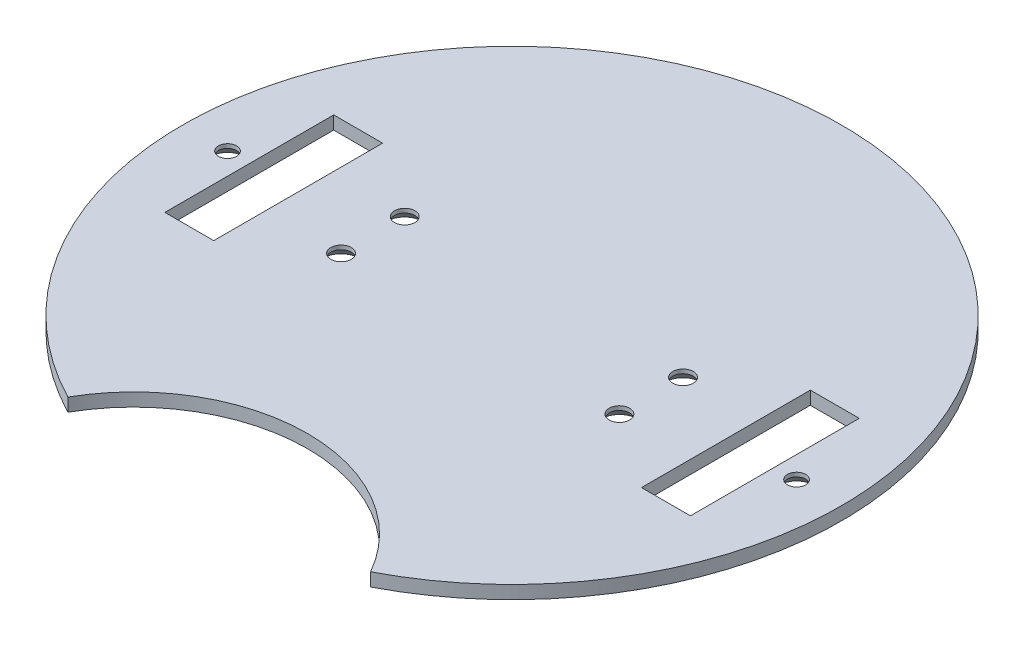
SolidWorks part; units mm, degrees
ref_plane "Front Plane" through (0, 0, 0) normal (0, 0, 1) x (1, 0, 0)
ref_plane "Top Plane" through (0, 0, 0) normal (0, 1, 0) x (1, 0, 0)
ref_plane "Right Plane" through (0, 0, 0) normal (1, 0, 0) x (0, 0, -1)
sketch "Sketch1" plane through (0, 0, 0) normal (0, 1, 0) x (1, 0, 0)
  line L0 (0, -83.2398) -> (-33.2911, -64.4046) construction
  line L1 (0, -83.2398) -> (0, 0) construction
  arc A0 (33.2911, -64.4046) -> (-33.2911, -64.4046) centre (0, 0) ccw
  arc A1 (33.2911, -64.4046) -> (-33.2911, -64.4046) centre (0, -83.2398) ccw
  dimension "D1" = 145
  dimension "D2" = 76.5
  dimension "D3" = 60.5
extrude "Boss-Extrude1" add sketch "Sketch1" along normal blind 2.9
sketch "solenoid placement" plane through (0, 2.9, 0) normal (0, 1, 0) x (1, 0, 0)
  line L0 (0, 0) -> (0, -36) construction
  line L1 (0, -36) -> (0, -44.9898) construction
  line L2 (-19, -36) -> (19, -36)
  line L3 (-19, -36) -> (-19, 28.4)
  line L4 (-19, 28.4) -> (19, 28.4)
  line L5 (19, -36) -> (19, 28.4)
  circle A1 centre (0, 0) radius 72.5 construction
  arc A2 (33.2911, -64.4046) -> (-33.2911, -64.4046) centre (0, 0) ccw construction
  arc A3 (33.2911, -64.4046) -> (-33.2911, -64.4046) centre (0, -83.2398) ccw construction
  dimension "D1" = 64.4
  dimension "D2" = 36
  dimension "D4" = 38
sketch "Sketch2" plane through (0, 2.9, 0) normal (0, 1, 0) x (1, 0, 0)
  line L1 (-57.5, 18.2695) -> (-47.34, 18.2695) construction
  line L2 (-57.5, 18.2695) -> (-57.5, -18.2695) construction
  line L3 (-57.5, -18.2695) -> (-47.34, -18.2695) construction
  line L4 (-47.34, 18.2695) -> (-47.34, -18.2695) construction
  line L8 (-57.8, -18.5695) -> (-47.04, -18.5695)
  line L9 (-47.04, 18.5695) -> (-47.04, -18.5695)
  line L10 (-57.8, 18.5695) -> (-47.04, 18.5695)
  line L11 (-57.8, 18.5695) -> (-57.8, -18.5695)
  line L12 (0, 0) -> (0, 72.5) construction
  line L13 (47.34, 18.2695) -> (47.34, -18.2695) construction
  line L14 (57.5, -18.2695) -> (47.34, -18.2695) construction
  line L15 (57.5, 18.2695) -> (57.5, -18.2695) construction
  line L16 (57.5, 18.2695) -> (47.34, 18.2695) construction
  line L17 (57.8, 18.5695) -> (57.8, -18.5695)
  line L18 (57.8, 18.5695) -> (47.04, 18.5695)
  line L19 (47.04, 18.5695) -> (47.04, -18.5695)
  line L20 (57.8, -18.5695) -> (47.04, -18.5695)
  arc A0 (33.2911, -64.4046) -> (-33.2911, -64.4046) centre (0, 0) ccw construction
extrude "Cut-Extrude1" cut sketch "Sketch2" against normal through all
sketch "Sketch3" plane through (0, 0, 0) normal (0, -1, 0) x (1, 0, 0)
  line L0 (0, 0) -> (0, -72.5) construction
  circle A0 centre (-62.58, 0) radius 2
  circle A1 centre (-30.61, 7) radius 2.25
  circle A2 centre (-30.61, -7) radius 2.25
  arc A3 (-33.2911, 64.4046) -> (33.2911, 64.4046) centre (0, 0) ccw construction
  circle A4 centre (30.61, -7) radius 2.25
  circle A5 centre (30.61, 7) radius 2.25
  circle A6 centre (62.58, 0) radius 2
  dimension "D1" = 4
  dimension "D2" = 4.5
extrude "Cut-Extrude2" cut sketch "Sketch3" against normal through all
chamfer "Chamfer1" distance 2 angle 41 6 edges at (-30.61, 0, -9.25) (-30.61, 0, 4.75) (-62.58, 0, -2) (62.58, 0, 2) (30.61, 0, 9.25) (30.61, 0, -4.75) first distance on face at (-30.61, 2.9, -9.25) first distance on face at (-30.61, 2.9, 4.75) first distance on face at (-62.58, 2.9, -2) first distance on face at (62.58, 2.9, 2) first distance on face at (30.61, 2.9, 9.25) first distance on face at (30.61, 2.9, -4.75)
equation "\"smallPulleyTeeth\"= 15"
equation "\"largePulleyTeeth\"= 40"
equation "\"eighthThick\"= 2.9mm"
equation "\"sixteenthThick\" = 1.7mm"
equation "\"quarterThick\"=5.9mm"
equation "\"OD\" = 145mm"
equation "\"puckAngle\" = 60.5deg"
equation "\"D1@Sketch1\"=\"OD\""
equation "\"puckDiam\" = 76.5mm"
equation "\"D2@Sketch1\"=\"puckDiam\""
equation "\"D3@Sketch1\"=\"puckAngle\""
equation "\"D1@Boss-Extrude1\"=\"eighthThick\""
equation "\"axlePress\" = 5.9mm"
equation "\"press\" = 0.2mm"
equation "\"wheelClear\" = 0.3mm"
equation "\"D1@Sketch2\"=\"wheelClear\""
equation "\"10-32clear\" = 4.5mm"
equation "\"6-32clear\" = 3.3mm"
equation "\"8-32clear\" = 4.0mm"
equation "\"wheelHeight\" = 24mm"
equation "\"D1@Sketch3\"=\"8-32clear\""
equation "\"D2@Sketch3\"=\"10-32clear\""
